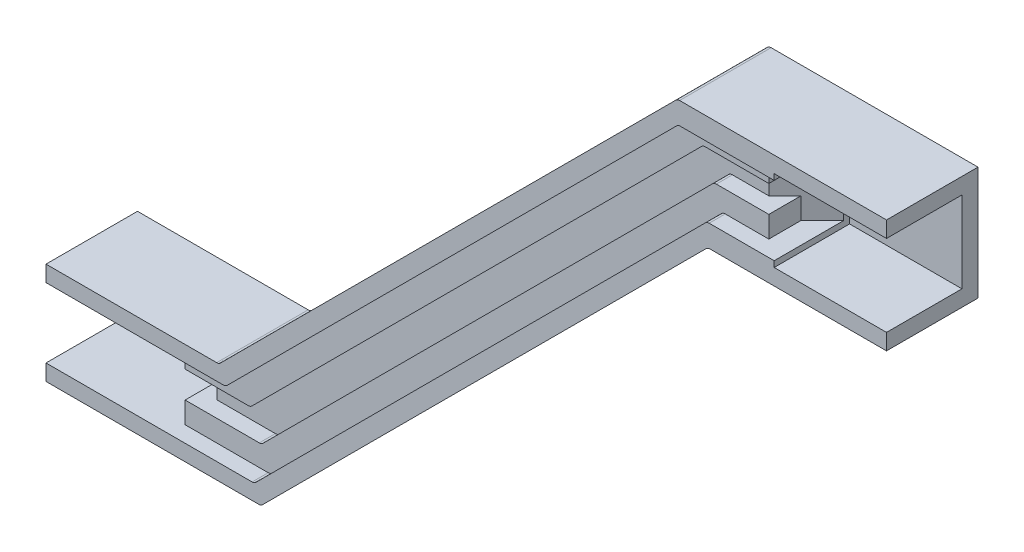
SolidWorks part; units mm, degrees
other "标注1"
sketch "草图9" plane through (0, 16, 0) normal (-0.9711, 0.0526, -0.2329) x (-0.2309, 0.0406, 0.9721)
ref_plane "前视基准面" through (0, 0, 0) normal (0, 0, 1) x (1, 0, 0)
ref_plane "上视基准面" through (0, 0, 0) normal (0, 1, 0) x (1, 0, 0)
ref_plane "右视基准面" through (0, 0, 0) normal (1, 0, 0) x (0, 0, -1)
sketch "草图10" plane through (0, 0, 0) normal (0, 0, 1) x (1, 0, 0)
  line L0 (-78.55, -32.8) -> (-46.235, -32.8)
  line L1 (-46.235, -32.8) -> (38.365, 51.8)
  line L2 (38.365, 51.8) -> (78.55, 51.8)
  line L3 (78.55, 51.8) -> (78.55, 32.8)
  line L4 (78.55, 32.8) -> (46.235, 32.8)
  line L5 (46.235, 32.8) -> (-38.365, -51.8)
  line L6 (-38.365, -51.8) -> (-78.55, -51.8)
  line L7 (-78.55, -51.8) -> (-78.55, -32.8)
  line L8 (-46.235, -32.8) -> (46.235, 32.8) construction
  line L9 (-38.365, -51.8) -> (38.365, 51.8) construction
  circle A0 centre (-68.55, -42.3) radius 1.65
  circle A1 centre (68.55, 42.3) radius 1.65
  dimension "D6" = 3.3
  dimension "D1" = 19
  dimension "D2" = 135
  dimension "D3" = 19
  dimension "D4" = 137.1
  dimension "D5" = 84.6
  dimension "D7" = 10
  dimension "D8" = 10
  dimension "D9" = 9.5
  dimension "D10" = 9.5
extrude "凸台-拉伸1" add sketch "草图10" along normal blind 3
sketch "草图11" plane through (0, 0, 0) normal (0, 0, 1) x (1, 0, 0)
  line L0 (-59.55, -32.8) -> (-59.55, -51.8)
  line L1 (-46.235, -32.8) -> (-78.55, -32.8) construction
  line L2 (-78.55, -51.8) -> (-38.365, -51.8) construction
  line L3 (-59.55, -32.8) -> (-46.235, -32.8)
  line L4 (-46.235, -32.8) -> (38.365, 51.8)
  line L5 (38.365, 51.8) -> (57.55, 51.8)
  line L7 (78.55, 51.8) -> (38.365, 51.8) construction
  line L8 (57.55, 51.8) -> (57.55, 32.8)
  line L9 (46.235, 32.8) -> (78.55, 32.8) construction
  line L10 (57.55, 32.8) -> (46.235, 32.8)
  line L11 (46.235, 32.8) -> (-38.365, -51.8)
  line L12 (-38.365, -51.8) -> (-59.55, -51.8)
  line L13 (-78.55, -32.8) -> (-78.55, -51.8) construction
  line L14 (78.55, 32.8) -> (78.55, 51.8) construction
  dimension "D1" = 19
  dimension "D2" = 21
extrude "凸台-拉伸2" add sketch "草图11" along normal blind 7 from surface at 3 starting at face at (0, 0, 3)
sketch "草图12" plane through (0, 0, 0) normal (0, 0, 1) x (1, 0, 0)
  line L0 (-78.55, -32.8) -> (-46.235, -32.8)
  line L1 (-46.235, -32.8) -> (-59.55, -32.8) construction
  line L2 (-46.235, -32.8) -> (38.365, 51.8)
  line L3 (38.365, 51.8) -> (78.55, 51.8)
  line L4 (78.55, 51.8) -> (78.55, 48.8)
  line L5 (78.55, 32.8) -> (78.55, 51.8) construction
  line L6 (78.55, 48.8) -> (39.6076, 48.8)
  line L7 (39.6076, 48.8) -> (-44.9924, -35.8)
  line L8 (-44.9924, -35.8) -> (-78.55, -35.8)
  line L9 (-78.55, -32.8) -> (-78.55, -51.8) construction
  line L10 (-78.55, -35.8) -> (-78.55, -32.8)
  line L11 (-78.55, -48.8) -> (-78.55, -51.8)
  line L12 (-78.55, -51.8) -> (-38.365, -51.8)
  line L13 (-38.365, -51.8) -> (46.235, 32.8)
  line L14 (46.235, 32.8) -> (78.55, 32.8)
  line L15 (57.55, 32.8) -> (78.55, 32.8) construction
  line L16 (78.55, 35.8) -> (44.9924, 35.8)
  line L17 (-78.55, -48.8) -> (-39.6076, -48.8)
  line L18 (-39.6076, -48.8) -> (44.9924, 35.8)
  line L19 (38.365, 51.8) -> (-46.235, -32.8) construction
  line L20 (78.55, 35.8) -> (78.55, 32.8)
  dimension "D1" = 3
  dimension "D2" = 3
extrude "凸台-拉伸3" add sketch "草图12" along normal blind 13 from surface at 3 starting at face at (-66.9, -42.3, 3)
chamfer "倒角1" distance 7 angle 45 2 edges at (57.55, 42.3, 10) (-59.55, -42.3, 10)
sketch "草图15" plane through (0, 0, 3) normal (0, 0, 1) x (1, 0, 0)
  line L0 (-55.55, -35.8) -> (-55.55, -39.8)
  line L1 (-78.55, -35.8) -> (-44.9924, -35.8) construction
  line L2 (-55.55, -39.8) -> (-43.3355, -39.8)
  line L3 (-43.3355, -39.8) -> (41.2645, 44.8)
  line L4 (41.2645, 44.8) -> (53.55, 44.8)
  line L5 (53.55, 44.8) -> (53.55, 48.8)
  line L6 (39.6076, 48.8) -> (78.55, 48.8) construction
  line L7 (53.55, 48.8) -> (39.6076, 48.8)
  line L8 (39.6076, 48.8) -> (-44.9924, -35.8)
  line L9 (-44.9924, -35.8) -> (-55.55, -35.8)
  line L10 (-55.55, -44.8) -> (-55.55, -48.8)
  line L11 (-52.55, -48.8) -> (-59.55, -48.8) construction
  line L12 (-55.55, -48.8) -> (-39.6076, -48.8)
  line L13 (-39.6076, -48.8) -> (44.9924, 35.8)
  line L14 (44.9924, 35.8) -> (53.55, 35.8)
  line L15 (78.55, 35.8) -> (44.9924, 35.8) construction
  line L16 (53.55, 35.8) -> (53.55, 39.8)
  line L17 (53.55, 39.8) -> (43.3355, 39.8)
  line L18 (43.3355, 39.8) -> (-41.2645, -44.8)
  line L19 (-41.2645, -44.8) -> (-55.55, -44.8)
  line L20 (-59.55, -35.8) -> (-59.55, -48.8) construction
  line L21 (57.55, 35.8) -> (57.55, 48.8) construction
  dimension "D1" = 4
  dimension "D2" = 4
  dimension "D3" = 4
  dimension "D4" = 4
  dimension "D5" = 4
extrude "凸台-拉伸5" add sketch "草图15" along normal blind 10
sketch "草图16" plane through (0, 0, 0) normal (0, 0, 1) x (1, 0, 0)
  line L0 (-78.55, -32.8) -> (-78.55, -51.8)
  line L1 (-78.55, -51.8) -> (-38.365, -51.8)
  line L2 (-38.365, -51.8) -> (45.135, 31.7)
  line L3 (45.135, 31.7) -> (78.55, 31.7)
  line L4 (78.55, 31.7) -> (78.55, 52.9)
  line L5 (78.55, 52.9) -> (39.465, 52.9)
  line L6 (39.465, 52.9) -> (-46.235, -32.8)
  line L7 (-46.235, -32.8) -> (-78.55, -32.8)
  line L8 (38.365, 51.8) -> (-46.235, -32.8) construction
  line L9 (-38.365, -51.8) -> (46.235, 32.8) construction
  line L11 (-46.235, -32.8) -> (-78.55, -32.8) construction
  line L12 (-78.55, -51.8) -> (-38.365, -51.8) construction
  line L13 (78.55, 51.8) -> (38.365, 51.8) construction
  line L14 (78.55, 35.8) -> (78.55, 48.8) construction
  circle A0 centre (-68.55, -42.3) radius 1.65
  circle A1 centre (68.55, 42.3) radius 1.65
  dimension "D3" = 3.3
  dimension "D1" = 21.2
  dimension "D2" = 1.1
extrude "凸台-拉伸6" add sketch "草图16" along normal blind 4.1 from offset 1.1 offset against normal yes
sketch "草图17" plane through (0, 0, 0) normal (0, 0, 1) x (1, 0, 0)
  line L12 (78.55, 52.9) -> (78.55, 48.8)
  line L13 (78.55, 48.8) -> (39.6076, 48.8)
  line L14 (39.6076, 48.8) -> (37.4863, 50.9213)
  line L15 (38.365, 51.8) -> (-46.235, -32.8) construction
  line L16 (37.4863, 50.9213) -> (39.465, 52.9)
  line L17 (39.465, 52.9) -> (78.55, 52.9)
  line L18 (78.55, 31.7) -> (45.135, 31.7)
  line L19 (-38.365, -51.8) -> (46.235, 32.8) construction
  line L20 (45.135, 31.7) -> (78.55, 31.7) construction
  line L21 (45.135, 31.7) -> (43.0137, 33.8213)
  line L22 (-39.6076, -48.8) -> (44.9924, 35.8) construction
  line L23 (43.0137, 33.8213) -> (44.9924, 35.8)
  line L24 (44.9924, 35.8) -> (78.55, 35.8)
  line L25 (78.55, 35.8) -> (44.9924, 35.8) construction
  line L26 (78.55, 35.8) -> (78.55, 31.7)
extrude "凸台-拉伸7" add sketch "草图17" along normal blind 16
sketch "草图18" plane through (0, 0, 16) normal (0, 0, 1) x (1, 0, 0)
  line L7 (78.55, 31.7) -> (78.55, 35.8) construction
  line L8 (57.55, 49.9) -> (78.55, 49.9)
  line L9 (57.55, 49.9) -> (57.55, 34.7)
  line L10 (57.55, 34.7) -> (78.55, 34.7)
  line L11 (78.55, 49.9) -> (78.55, 34.7)
  line L12 (78.55, 52.9) -> (39.465, 52.9) construction
  line L13 (45.135, 31.7) -> (78.55, 31.7) construction
  dimension "D1" = 3
  dimension "D2" = 3
  dimension "D3" = 21
extrude "切除-拉伸1" cut sketch "草图18" against normal blind 14.1
fillet "圆角1" radius 1 12 edges at (-39.6076, -48.8, 14.5) (-41.2645, -44.8, 11.5) (43.3355, 39.8, 11.5) (44.9924, 35.8, 14.5) (41.2645, 44.8, 11.5) (39.6076, 48.8, 14.5) (-43.3355, -39.8, 11.5) (-44.9924, -35.8, 14.5) (-46.235, -32.8, 7.45) (-38.365, -51.8, 7.45) (39.465, 52.9, 7.45) (45.135, 31.7, 7.45)
